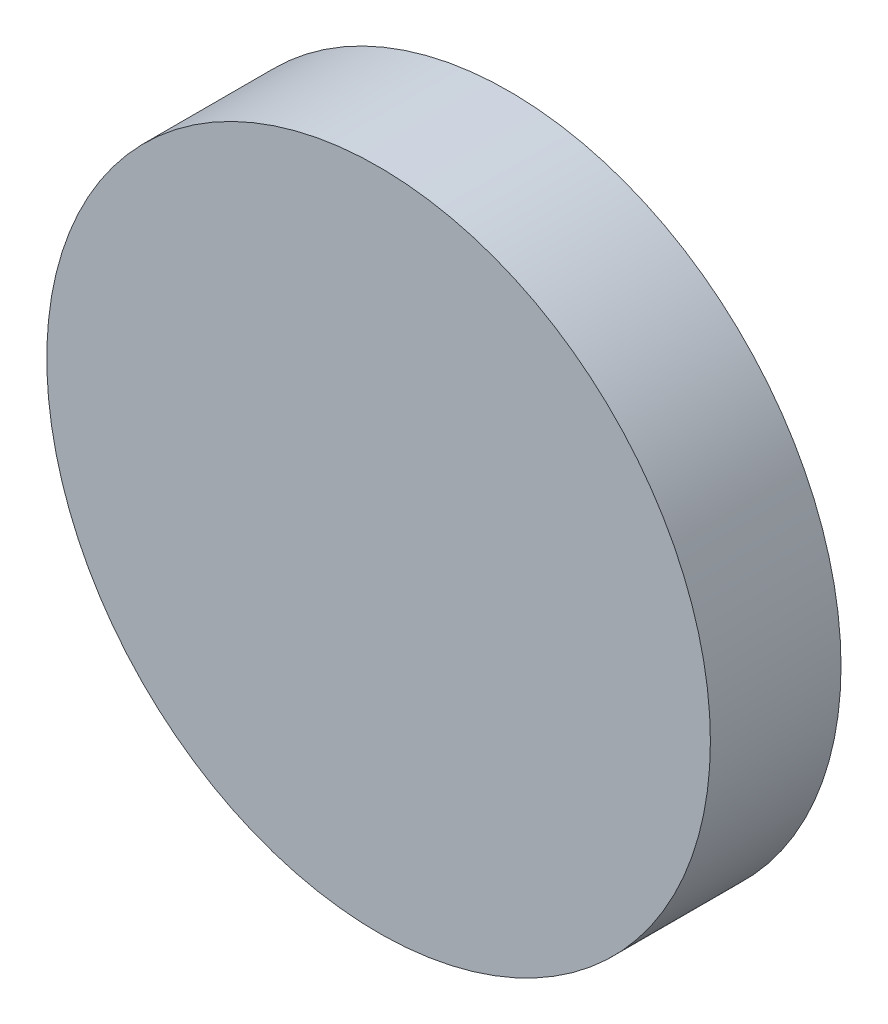
SolidWorks part; units mm, degrees
material "Natural Rubber"
ref_plane "Front Plane" through (0, 0, 0) normal (0, 0, 1) x (1, 0, 0)
ref_plane "Top Plane" through (0, 0, 0) normal (0, 1, 0) x (1, 0, 0)
ref_plane "Right Plane" through (0, 0, 0) normal (1, 0, 0) x (0, 0, -1)
sketch "Sketch1" plane through (0, 0, 0) normal (0, 0, 1) x (1, 0, 0)
  circle A0 centre (0, 0) radius 38.1
  dimension "D1" = 76.2
extrude "Boss-Extrude1" add sketch "Sketch1" along normal blind 15
hole_wizard "Ø3.0mm Clearance Dowel Hole1" positions "Sketch2" profile "Sketch3" hole size "Ø3.0" standard "ANSI Metric" end condition through all
sketch "Sketch2" plane through (0, 0, 15) normal (0, 0, 1) x (1, 0, 0)
  point P0 (0, 0)
sketch "Sketch3" plane through (0, 0, 15) normal (1, 0, 0) x (0, -1, 0)
  line L0 (0, 0) -> (0, 15)
  line L1 (0, 15) -> (1.5, 15)
  line L2 (1.5, 15) -> (1.5, 0)
  line L5 (1.5, 0) -> (0, 0)
  line L11 (0, -6.35) -> (0, 107.95) construction
  dimension "Thru Hole Dia." = 3
  dimension "Thru Hole Depth" = 15
shell "Shell3" thickness 5 removed face at (1.5, 0, 15)
extrude "Boss-Extrude2" add sketch "Sketch1<2>" against normal blind 5 from surface starting at face at (33.1, 0, 15)
sketch "Sketch1<2>" plane through (0, 0, 0) normal (0, 0, 1) x (1, 0, 0) same geometry as "Sketch1"
